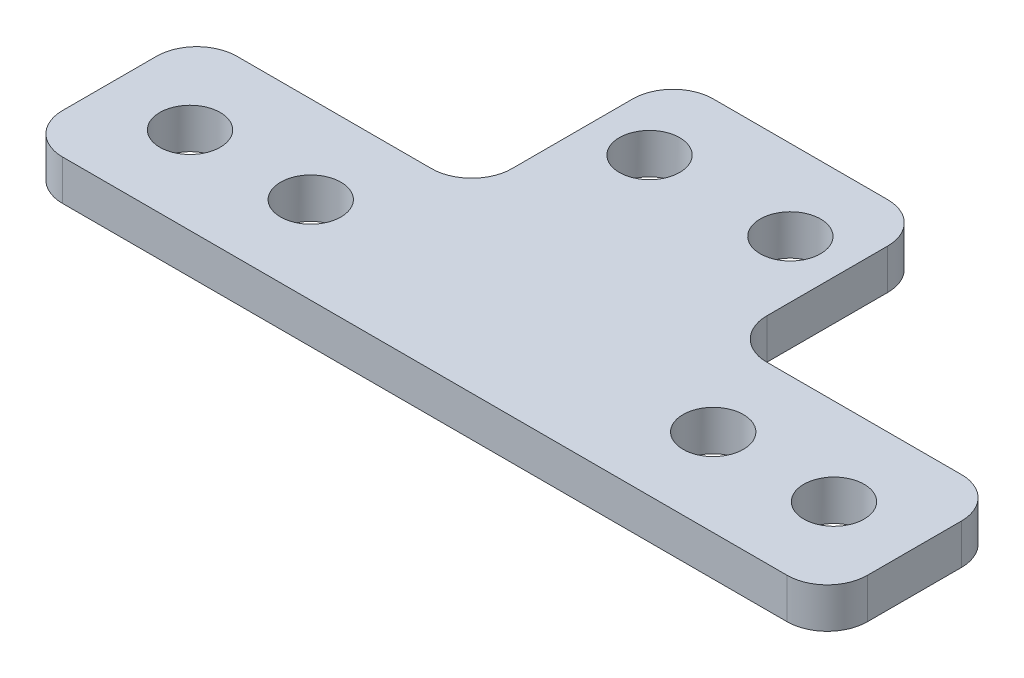
SolidWorks part; units mm, degrees
material "6063-T1"
ref_plane "Płaszczyzna przednia" through (0, 0, 0) normal (0, 0, 1) x (1, 0, 0)
ref_plane "Płaszczyzna górna" through (0, 0, 0) normal (0, 1, 0) x (1, 0, 0)
ref_plane "Płaszczyzna prawa" through (0, 0, 0) normal (1, 0, 0) x (0, 0, -1)
sketch "Szkic1" plane through (0, 0, 0) normal (0, 1, 0) x (1, 0, 0)
  line L5 (9.5, 15) -> (-9.5, 15)
  line L6 (0, 0) -> (0, 26737.7649) construction
  line L7 (-9.5, 15) -> (-9.5, 0)
  line L8 (-9.5, 0) -> (-30, 0)
  line L9 (-30, 0) -> (-30, -13)
  line L10 (9.5, 15) -> (9.5, 0)
  line L11 (9.5, 0) -> (30, 0)
  line L12 (30, 0) -> (30, -13)
  line L13 (-30, -13) -> (30, -13)
  dimension "D1" = 28
  dimension "D2" = 13
  dimension "D3" = 19
  dimension "D4" = 60
base flange "Odgięcie bazowe1" sketch "Szkic1" thickness 3 reverse thickness direction no parameters "D1"=2
hole_wizard "Otwór pod śrubę M41" positions "Szkic8" profile "Szkic9" hole size "M4" standard "Ansi Metric"
sketch "Szkic8" plane through (0, 0, 0) normal (0, 1, 0) x (1, 0, 0)
  line L0 (0, 0) -> (0, 50000) construction
  line L1 (9.5, 15) -> (-9.5, 15) construction
  line L2 (-30, -6.5) -> (-15, -6.5) construction
  line L3 (-30, 0) -> (-30, -13) construction
  point P0 (-5.25, 9)
  point P7 (5.25, 9)
  point P10 (-15, -6.5)
  point P15 (15, -6.5)
  point P21 (-24, -6.5)
  point P25 (24, -6.5)
  dimension "D1" = 10.5
  dimension "D2" = 6
  dimension "D3" = 30
  dimension "D4" = 48
sketch "Szkic9" plane through (-5.25, 0, -9) normal (1, 0, 0) x (0, 0, 1)
  line L0 (0, 0) -> (0, 11.3519)
  line L1 (0, 11.3519) -> (2.25, 10)
  line L2 (2.25, 10) -> (2.25, 0)
  line L5 (2.25, 0) -> (0, 0)
  line L10 (0, 11.3519) -> (-2.25, 10) construction
  line L11 (0, -6.35) -> (0, 107.95) construction
  dimension "Średnica otworu" = 4.5
  dimension "Głębokość otworu" = 10
  dimension "Kąt wiertła" = 118
fillet "Zaokrąglenie1" radius 3 8 edges at (-9.5, -1.5, 0) (9.5, -1.5, 0) (-9.5, -1.5, -15) (9.5, -1.5, -15) (30, -1.5, 13) (30, -1.5, 0) (-30, -1.5, 13) (-30, -1.5, 0)
sketch "Linie zgięcia1" [suppressed] plane through (0, 0, 0) normal (0, 1, 0) x (1, 0, 0)
sketch "Ramka-graniczna1" [suppressed] plane through (0, 0, 0) normal (0, 1, 0) x (1, 0, 0)
sheet metal parameters "Arkusz blachy2" thickness 3 parameters "D1"=2
flat pattern "Rozłożony model2" [suppressed]
sketch "Linie zgięcia2" plane through (0, 0, 0) normal (0, 1, 0) x (1, 0, 0)
sketch3d "Ramka-graniczna2" [suppressed]
  line L0 (11.5, 16.5, 0) -> (11.5, -16.5, 0) construction
  line L1 (-11.5, 16.5, 0) -> (-11.5, -16.5, 0) construction
  line L2 (11.5, 16.5, 0) -> (-11.5, 16.5, 0) construction
  line L3 (11.5, -16.5, 0) -> (-11.5, -16.5, 0) construction
sheet metal parameters "Arkusz blachy3" thickness 3 parameters "D1"=2
flat pattern "Rozłożony model2"
sketch "Linie zgięcia2" plane through (0, 0, 0) normal (0, 1, 0) x (1, 0, 0)
sketch3d "Ramka-graniczna2" [suppressed]
  line L0 (30, 15, 0) -> (-30, 15, 0) construction
  line L1 (30, -13, 0) -> (-30, -13, 0) construction
  line L2 (30, 15, 0) -> (30, -13, 0) construction
  line L3 (-30, 15, 0) -> (-30, -13, 0) construction
